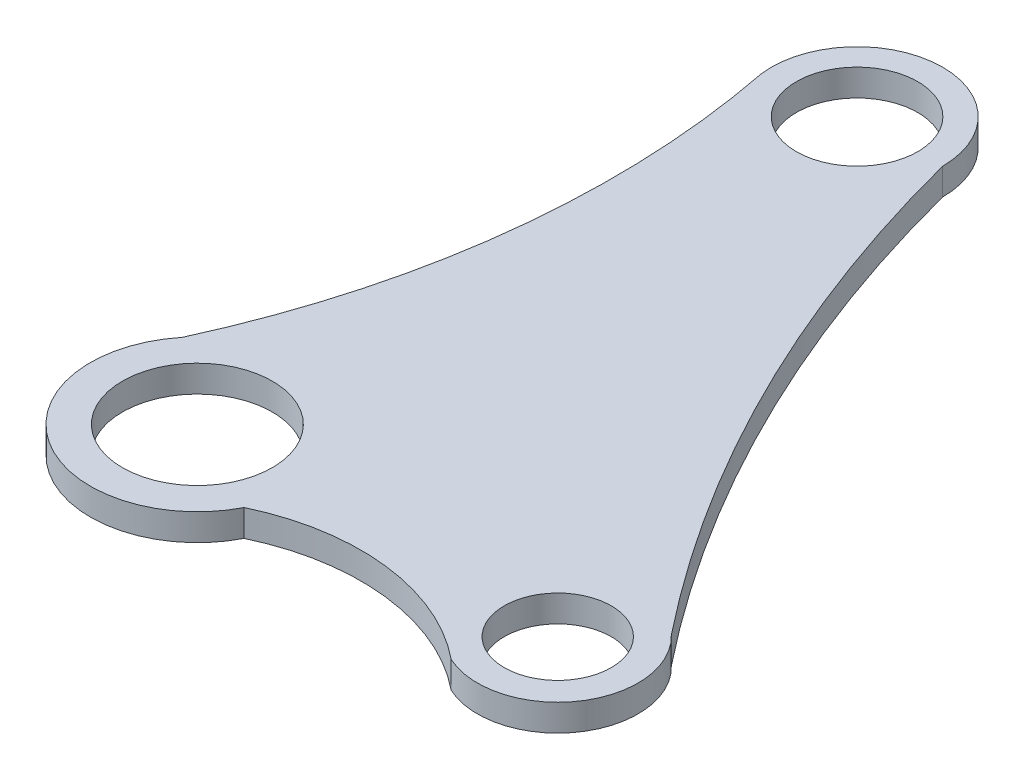
SolidWorks part; units mm, degrees
ref_plane "Front Plane" through (0, 0, 0) normal (0, 0, 1) x (1, 0, 0)
ref_plane "Top Plane" through (0, 0, 0) normal (0, 1, 0) x (1, 0, 0)
ref_plane "Right Plane" through (0, 0, 0) normal (1, 0, 0) x (0, 0, -1)
sketch "Sketch1" plane through (0, 0, 0) normal (0, 1, 0) x (1, 0, 0)
  circle A0 centre (0, 0) radius 12.7
  circle A1 centre (7.5123, 70.7221) radius 10.16
  circle A2 centre (43.1778, -0.4392) radius 9.525
  arc A3 (-2.5703, 69.4703) -> (-9.8419, 8.0266) centre (-101.3163, 50.0043) cw
  arc A4 (17.6723, 70.7221) -> (49.7515, 6.4537) centre (185.3377, 114.271) ccw
  arc A5 (11.3158, -5.7657) -> (39.2012, -9.0944) centre (22.6244, -29.496) cw
  circle A6 centre (7.5123, 70.7221) radius 7.1995
  circle A7 centre (0, 0) radius 8.89
  circle A8 centre (43.1778, -0.4392) radius 6.35
  point P19 (-9.8419, 8.0266)
  dimension "D1" = 20.32
  dimension "D2" = 25.4
  dimension "D3" = 19.05
  dimension "D5" = 43.18
  dimension ".8" = 71.12
extrude "Boss-Extrude1" add sketch "Sketch1" along normal blind 3.175 contours A0 A5 A2 A1 | A0 A7 | A1 A6 | A2 A8 region at (11.9998, 0, 2.8809) region at (16.9078, 0, -27.7429) region at (-2.1633, 0, -68.8802) region at (36.6053, 0, -6.0776)
ref_point "pivot pt"
ref_point "shock pt"
